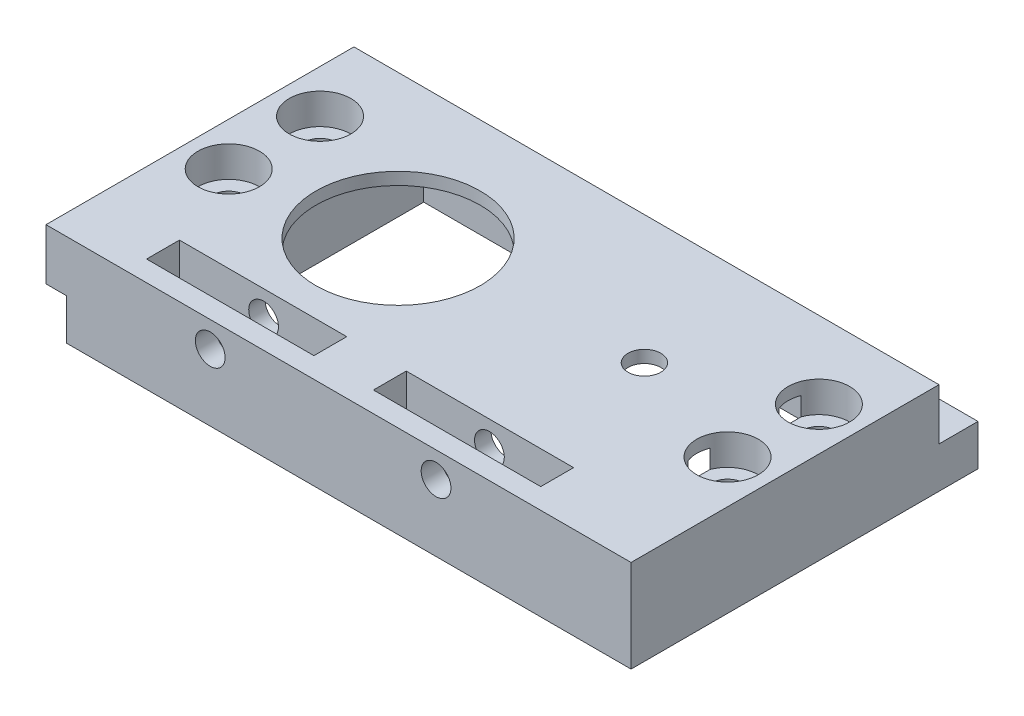
SolidWorks part; units mm, degrees
ref_plane "Front Plane" through (0, 0, 0) normal (0, 0, 1) x (1, 0, 0)
ref_plane "Top Plane" through (0, 0, 0) normal (0, 1, 0) x (1, 0, 0)
ref_plane "Right Plane" through (0, 0, 0) normal (1, 0, 0) x (0, 0, -1)
sketch "Sketch1" plane through (0, 0, 0) normal (0, 1, 0) x (1, 0, 0)
  line L0 (-11.25, 0) -> (11.25, 0)
  line L1 (-25, 12.5) -> (25, 12.5)
  line L2 (-25, 12.5) -> (-25, -12.5)
  line L3 (-25, -12.5) -> (25, -12.5)
  line L4 (25, 12.5) -> (25, -12.5)
  line L5 (-25, 12.5) -> (25, -12.5) construction
  line L6 (-25, -12.5) -> (25, 12.5) construction
  circle A0 centre (11.25, 0) radius 4.5
  circle A1 centre (-11.25, 0) radius 1.3
  point P0 (0, 0)
  point P9 (0, 0)
  dimension "D4" = 9
  dimension "D5" = 2.6
  dimension "D1" = 50
  dimension "D2" = 25
  dimension "D3" = 22.5
extrude "Boss-Extrude2" add sketch "Sketch1" along normal mid plane 5 contours L4 L1 L2 L3 A1 A0 region at (0, 0, -11.941)
sketch "Sketch5" plane through (0, 0, 12.5) normal (0, 0, 1) x (1, 0, 0)
  line L1 (-25, -2.5) -> (25, -2.5)
  line L2 (-25, -2.5) -> (-25, 9.5)
  line L3 (-25, 9.5) -> (25, 9.5)
  line L4 (25, -2.5) -> (25, 9.5)
  dimension "D1" = 50
  dimension "D2" = 12
extrude "Boss-Extrude3" add sketch "Sketch5" along normal mid plane 3
sketch "Sketch6" plane through (0, 9.5, 0) normal (0, 1, 0) x (1, 0, 0)
  line L1 (-25, 12.5) -> (25, 12.5)
  line L2 (-25, 12.5) -> (-25, -14)
  line L3 (-25, -14) -> (25, -14)
  line L4 (25, 12.5) -> (25, -14)
extrude "Boss-Extrude4" add sketch "Sketch6" along normal mid plane 3
sketch "Sketch7" plane through (0, 11, 0) normal (0, 1, 0) x (1, 0, 0)
  line L0 (0, 0) -> (0, 8.4182) construction
  line L1 (-25, 12.5) -> (-25, -14) construction
  circle A0 centre (-11.25, 0) radius 1.3
  circle A1 centre (11.25, 0) radius 1.3
  dimension "D2" = 2.6
  dimension "D1" = 13.75
extrude "Cut-Extrude3" cut sketch "Sketch7" against normal blind 23
sketch "Sketch8" plane through (0, -2.5, 0) normal (0, -1, 0) x (1, 0, 0)
  line L1 (-5.05, 14.7) -> (47.95, 14.7)
  line L2 (-5.05, 14.7) -> (-5.05, -17.8)
  line L3 (-5.05, -17.8) -> (47.95, -17.8)
  line L4 (47.95, 14.7) -> (47.95, -17.8)
  line L5 (0.95, 8.7) -> (0.95, -12.8) construction
  line L6 (0.45, 9.2) -> (42.45, 9.2)
  line L7 (0.45, 9.2) -> (0.45, -13.3)
  line L8 (0.45, -13.3) -> (42.45, -13.3)
  line L9 (42.45, 9.2) -> (42.45, -13.3)
  line L10 (0.95, -12.8) -> (41.95, -12.8) construction
  line L11 (41.95, 8.7) -> (41.95, -12.8) construction
  line L12 (0.95, 8.7) -> (41.95, 8.7) construction
  line L13 (-25, 14) -> (25, 14) construction
  line L14 (-25, -12.5) -> (-25, 14) construction
  line L15 (21.45, 8.7) -> (21.45, -12.8) construction
  line L16 (21.45, -2.05) -> (25.896, -2.05) construction
  circle A0 centre (45.75, -6.5) radius 1.6
  circle A1 centre (45.75, 2.4) radius 1.6
  circle A2 centre (-2.85, -6.5) radius 1.6
  circle A3 centre (-2.85, 2.4) radius 1.6
  circle A5 centre (11.25, 0) radius 8
  line M15 (25, -12.5) -> (25, 14)
  line M16 (25, 14) -> (-25, 14)
  line M18 (-25, -12.5) -> (25, -12.5)
  dimension "D10" = 3.2
  dimension "D11" = 16
  dimension "D2" = 32.5
  dimension "D3" = 5.5
  dimension "D4" = 5.5
  dimension "D5" = 22.5
  dimension "D6" = 0.7
  dimension "D7" = 19.95
  dimension "D8" = 3.8
  dimension "D9" = 11.3
  dimension "D13" = 42
  dimension "D14" = 53
  dimension "D1" = 0.5
extrude "Boss-Extrude5" add sketch "Sketch8" along normal blind 4 contours L6 L9 L8 L7 L2 L3 L4 L1 A0 A1 M18 M16 M15 | L7 L6 L2 A3 A2 M15 M16 M18 region at (21.45, -2.5, 14.0783) region at (9.975, -2.5, 13.5993)
extrude "Cut-Extrude4" cut sketch "Sketch8<3>" against normal up to surface (5 mm away) contours A5 up to face at (0, 2.5, -0.75)
sketch "Sketch8<3>" plane through (0, -2.5, 0) normal (0, -1, 0) x (1, 0, 0) same geometry as "Sketch8"
sketch "Sketch9" plane through (0, -2.5, 0) normal (0, -1, 0) x (1, 0, 0)
  line L1 (0.45, 9.2) -> (25, 9.2)
  line L2 (0.45, 9.2) -> (0.45, -12.5)
  line L3 (0.45, -12.5) -> (25, -12.5)
  line L4 (25, 9.2) -> (25, -12.5)
extrude "Cut-Extrude5" cut sketch "Sketch9" against normal blind 3.8
sketch "Sketch10" plane through (25, 0, 0) normal (1, 0, 0) x (0, 0, -1)
  line L0 (-14.7, -2.5) -> (-14.7, 2.5)
  line L1 (-14.7, 2.5) -> (14, 2.5)
  line L2 (14, 2.5) -> (14, -2.5)
  line L3 (-14.7, -2.5) -> (17.8, -2.5) construction
  line L4 (14, -2.5) -> (12.3, -2.5)
  line L5 (12.3, -2.5) -> (12.3, 1.3)
  line L6 (12.3, 1.3) -> (-9.2, 1.3)
  line L7 (-9.2, 1.3) -> (-9.2, -2.5)
  line L8 (-9.2, -2.5) -> (-14, -2.5) construction
  line L9 (-9.2, -2.5) -> (-14.7, -2.5)
  dimension "D1" = 5
  dimension "D2" = 28.7
  dimension "D3" = 5.5
  dimension "D4" = 21.5
  dimension "D5" = 3.8
  dimension "D6" = 1.7
extrude "Boss-Extrude6" add sketch "Sketch10" along normal up to surface (22.95 mm away) up to face at (47.95, -4.5, -1.55)
sketch "Sketch11" plane through (47.95, 0, 0) normal (1, 0, 0) x (0, 0, -1)
  line L0 (-14.7, 2.5) -> (14, 2.5)
  line L1 (14, 2.5) -> (14, -2.5)
  line L2 (14, -2.5) -> (17.8, -2.5)
  line L3 (17.8, -2.5) -> (17.8, -6.5)
  line L4 (17.8, -6.5) -> (-14.7, -6.5)
  line L5 (-14.7, -6.5) -> (-14.7, 2.5)
extrude "Boss-Extrude7" add sketch "Sketch11" along normal blind 2
extrude "Cut-Extrude6" cut sketch "Sketch8<4>" against normal blind 5 contours A0 | A1 | A3 | A2
sketch "Sketch8<4>" plane through (0, -2.5, 0) normal (0, -1, 0) x (1, 0, 0) same geometry as "Sketch8"
sketch "Sketch12" plane through (0, 1.3, 0) normal (0, -1, 0) x (1, 0, 0)
  line L0 (49.95, 14.7) -> (49.95, -17.8) construction
  line L1 (49.95, 8.7) -> (42.95, 8.7)
  line L2 (49.95, 8.7) -> (49.95, -12.3)
  line L3 (49.95, -12.3) -> (42.95, -12.3)
  line L4 (42.95, 8.7) -> (42.95, -12.3)
  line L5 (42.45, -12.3) -> (25, -12.3) construction
  line L6 (0.45, 9.2) -> (0.45, -12.5) construction
  dimension "D1" = 42.5
  dimension "D2" = 21
extrude "Boss-Extrude8" add sketch "Sketch12" along normal up to surface (7.8 mm away) up to face at (21.45, -6.5, -2.05)
sketch "Sketch13" plane through (0, 0, 0) normal (1, 0, 0) x (0, 0, -1)
  line L0 (-14, -2.5) -> (-14, 2.5) construction
  line L1 (-14.7, -6.5) -> (-14, -6.5)
  line L2 (-14.7, -6.5) -> (-14.7, 2.5)
  line L3 (-14.7, 2.5) -> (-14, 2.5)
  line L4 (-14, -6.5) -> (-14, 2.5)
  line L5 (-14, 11) -> (-14, -2.5) construction
extrude "Cut-Extrude7" cut sketch "Sketch13" against normal through all both and the other way through all
sketch "Sketch14" plane through (0, 0, 0) normal (1, 0, 0) x (0, 0, -1)
  line L1 (12.5, 11) -> (-14, 11)
  line L2 (12.5, 11) -> (12.5, 2.5)
  line L3 (12.5, 2.5) -> (-14, 2.5)
  line L4 (-14, 11) -> (-14, 2.5)
extrude "Cut-Extrude8" cut sketch "Sketch14" against normal through all both and the other way through all
sketch "Sketch15" plane through (0, 2.5, 0) normal (0, 1, 0) x (1, 0, 0)
  circle A0 centre (-2.85, 6.5) radius 3
  circle A1 centre (-2.85, -2.4) radius 3
  circle A2 centre (45.75, 6.5) radius 3
  circle A3 centre (45.75, -2.4) radius 3
  dimension "D1" = 6
extrude "Cut-Extrude9" cut sketch "Sketch15" against normal blind 3 and the other way through all
extrude "Cut-Extrude10" cut sketch "Sketch8<5>" against normal through all both and the other way through all contours A0 | A1
sketch "Sketch8<5>" plane through (0, -2.5, 0) normal (0, -1, 0) x (1, 0, 0) same geometry as "Sketch8"
sketch "Sketch16" plane through (0, 0, 14) normal (0, 0, 1) x (1, 0, 0)
  line L0 (-25, 2.5) -> (49.95, 2.5) construction
  line L1 (-5.05, -2.5) -> (0.75, -2.5)
  line L2 (-5.05, -2.5) -> (-5.05, 2.5)
  line L3 (-5.05, 2.5) -> (0.75, 2.5)
  line L4 (0.75, -2.5) -> (0.75, 2.5)
  line L6 (17.05, 2.5) -> (22.85, 2.5)
  line L7 (17.05, 2.5) -> (17.05, -2.5)
  line L8 (17.05, -2.5) -> (22.85, -2.5)
  line L9 (22.85, 2.5) -> (22.85, -2.5)
  line L10 (44.95, 2.5) -> (39.15, 2.5)
  line L11 (44.95, 2.5) -> (44.95, -2.5)
  line L12 (44.95, -2.5) -> (39.15, -2.5)
  line L13 (39.15, 2.5) -> (39.15, -2.5)
  line L14 (0.75, 2.5) -> (17.05, 2.5)
  line L15 (0.75, 2.5) -> (0.75, -2.5)
  line L16 (0.75, -2.5) -> (17.05, -2.5)
  line L17 (17.05, 2.5) -> (17.05, -2.5)
  line L18 (22.85, 2.5) -> (39.15, 2.5)
  line L19 (22.85, 2.5) -> (22.85, -2.5)
  line L20 (22.85, -2.5) -> (39.15, -2.5)
  line L21 (39.15, 2.5) -> (39.15, -2.5)
  line M8 (49.95, 2.5) -> (-25, 2.5)
  dimension "D1" = 50
  dimension "D2" = 5.8
  dimension "D3" = 5.8
  dimension "D4" = 5.8
  dimension "D5" = 16.3
extrude "Cut-Extrude11" cut sketch "Sketch16" against normal blind 3.2 contours L4 L16 L7 M8 | L9 L20 L13 M8 region at (8.9, 0, 14) region at (31, 0, 14)
sketch "Sketch17" plane through (0, 0, 0) normal (0, 0, 1) x (1, 0, 0)
  line L0 (17.05, 2.5) -> (0.75, 2.5) construction
  line L1 (39.15, 2.5) -> (22.85, 2.5) construction
  circle A0 centre (8.95, 0) radius 1.45
  circle A1 centre (30.95, 0) radius 1.45
  dimension "D1" = 2.9
  dimension "D2" = 2.9
  dimension "D3" = 14
  dimension "D4" = 22
  dimension "D5" = 2.5
  dimension "D6" = 2.5
extrude "Cut-Extrude12" cut sketch "Sketch17" along normal blind 13.2
sketch "Sketch18" plane through (0, 2.5, 0) normal (0, 1, 0) x (1, 0, 0)
  line L0 (39.15, -10.8) -> (22.85, -10.8) construction
  line L1 (0.75, -10.8) -> (0.75, -14) construction
  circle A0 centre (33.75, 1.5) radius 1.6
  dimension "D1" = 3.2
  dimension "D2" = 12.3
  dimension "D3" = 33
extrude "Cut-Extrude13" cut sketch "Sketch18" against normal blind 3.2
sketch "Sketch19" plane through (0, 0, 14) normal (0, 0, 1) x (1, 0, 0)
  line L0 (-25, -2.5) -> (-5.05, -2.5) construction
  line L1 (-7.05, -2.5) -> (-25, -2.5)
  line L2 (-7.05, -2.5) -> (-7.05, 2.5)
  line L3 (-7.05, 2.5) -> (-25, 2.5)
  line L4 (-25, -2.5) -> (-25, 2.5)
  line L5 (-5.05, -6.5) -> (-5.05, -2.5) construction
  dimension "D1" = 2
extrude "Cut-Extrude14" cut sketch "Sketch19" against normal blind 33.2
sketch "Sketch20" plane through (0, 0, 14) normal (0, 0, 1) x (1, 0, 0)
  line L0 (-7.05, 2.5) -> (49.95, 2.5)
  line L1 (49.95, 2.5) -> (49.95, -6.5)
  line L2 (49.95, -6.5) -> (-5.05, -6.5)
  line L3 (-5.05, -6.5) -> (-5.05, -2.5)
  line L4 (-5.05, -2.5) -> (-7.05, -2.5)
  line L5 (-7.05, -2.5) -> (-7.05, 2.5)
extrude "Boss-Extrude9" add sketch "Sketch20" along normal blind 2
sketch "Sketch21" plane through (25, 0, 0) normal (-1, 0, 0) x (0, 0, 1)
  line L0 (-12.3, -2.5) -> (-13.3, -2.5) construction
  line L1 (-14, 2.5) -> (-12.5, 2.5)
  line L2 (-14, 2.5) -> (-14, -2.5)
  line L3 (-14, -2.5) -> (-12.5, -2.5)
  line L4 (-12.5, 2.5) -> (-12.5, -2.5)
  line L5 (-12.5, 2.5) -> (-12.5, -2.5) construction
extrude "Boss-Extrude10" add sketch "Sketch21" along normal up to surface (32.05 mm away) up to face at (-7.05, 0, 1.75)
sketch "Sketch23" plane through (0, 0, 0) normal (1, 0, 0) x (0, 0, -1)
  line L1 (12.5, 1.3) -> (12.3, 1.3)
  line L2 (12.5, 1.3) -> (12.5, -2.5)
  line L3 (12.5, -2.5) -> (12.3, -2.5)
  line L4 (12.3, 1.3) -> (12.3, -2.5)
extrude "Cut-Extrude15" cut sketch "Sketch23" along normal up to surface (42.95 mm away) up to face at (42.95, 0.0667, -1.9667)
extrude "Cut-Extrude16" cut sketch "Sketch17<2>" along normal blind 20
sketch "Sketch17<2>" plane through (0, 0, 0) normal (0, 0, 1) x (1, 0, 0) same geometry as "Sketch17"
